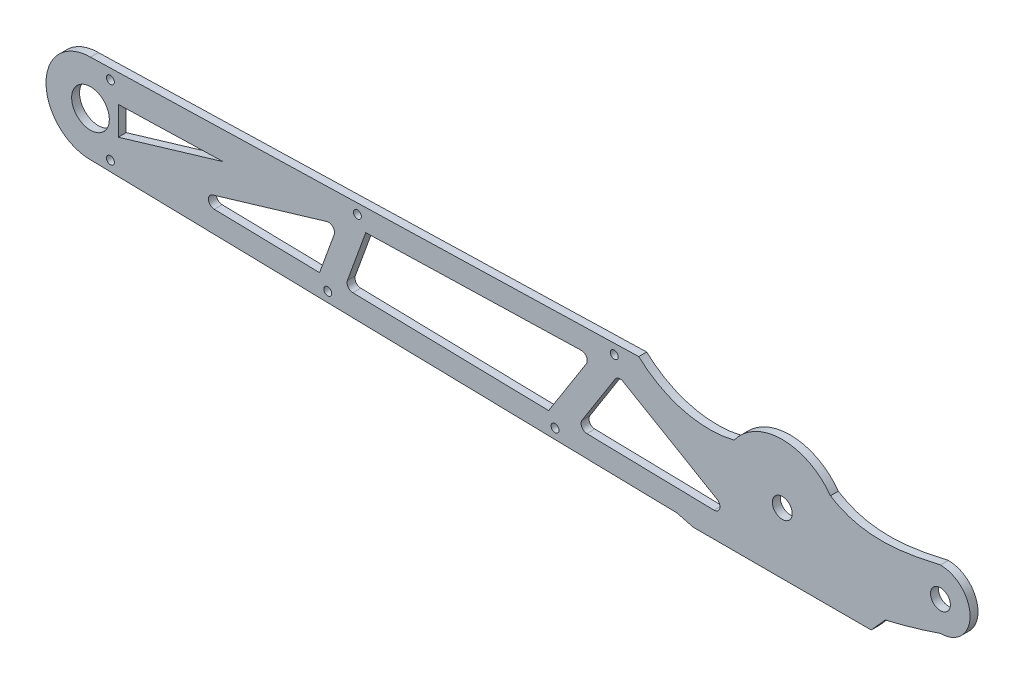
SolidWorks part; units mm, degrees
ref_plane "前视基准面" through (0, 0, 0) normal (0, 0, 1) x (1, 0, 0)
ref_plane "上视基准面" through (0, 0, 0) normal (0, 1, 0) x (1, 0, 0)
ref_plane "右视基准面" through (0, 0, 0) normal (1, 0, 0) x (0, 0, -1)
sketch "草图1" plane through (0, 0, 0) normal (0, 0, 1) x (1, 0, 0)
  line L1 (-1.4571, -0.1457) -> (348.5429, -0.1457) construction
  line L4 (348.5429, -0.1457) -> (428.5429, -0.1457) construction
  line L9 (-1.4571, -22.6457) -> (348.5429, -30.1457)
  line L10 (275.9324, 29.8543) -> (-1.4571, 22.3543)
  circle A0 centre (428.5429, -0.1457) radius 5.03
  circle A1 centre (-1.4571, -0.1457) radius 9.53
  circle A4 centre (-1.4571, -0.1457) radius 22.5 construction
  circle A11 centre (348.5429, -0.1457) radius 5.03
  circle A14 centre (348.5429, -0.1457) radius 30 construction
  circle A15 centre (428.5429, -0.1457) radius 15 construction
  arc A16 (428.5429, -15.1457) -> (428.5429, 14.8543) centre (428.5429, -0.1457) ccw
  arc A18 (372.8996, 17.3685) -> (324.1861, 17.3685) centre (348.5429, -0.1457) ccw
  arc A19 (428.5429, -15.1457) -> (348.5429, -30.1457) centre (338.2377, 245.6483) cw
  arc A20 (324.1861, 17.3685) -> (275.9324, 29.8543) centre (311.6087, 68.2465) cw
  arc A21 (-1.4571, -22.6457) -> (-1.4571, 22.3543) centre (-1.4571, -0.1457) cw
  spline S0 degree 3 poles (428.5429, 14.8543) (410.6193, 10.8049) (389.6426, 6.6246) (372.8996, 17.3685) knots 0 0 0 0 1 1 1 1
  dimension "D1" = 350
  dimension "D2" = 10.06
  dimension "D3" = 19.06
  dimension "D4" = 10.06
  dimension "D5" = 45
  dimension "D7" = 80
extrude "凸台-拉伸1" add sketch "草图1" along normal blind 4
sketch "草图2" plane through (0, 0, 4) normal (0, 0, 1) x (1, 0, 0)
  line L0 (348.5429, -30.1457) -> (348.5429, -25.1457)
  line L2 (-1.4571, -0.1457) -> (348.5429, -0.1457) construction
  circle A0 centre (348.5429, -25.1457) radius 2 construction
  circle A1 centre (233.5693, -22.682) radius 2
  circle A2 centre (118.5956, -20.2183) radius 2
  circle A3 centre (3.622, -17.7546) radius 2 construction
  circle A4 centre (3.622, 17.4631) radius 2 construction
  circle A5 centre (133.5745, 20.9768) radius 2
  circle A6 centre (263.5271, 24.4904) radius 2
  circle A7 centre (8.622, -17.7546) radius 2
  circle A8 centre (8.622, 17.4631) radius 2
  dimension "D1" = 4
  dimension "D3" = 5
  dimension "D2" = 3
extrude "切除-拉伸1" cut sketch "草图2" against normal blind 4 contours A3 | A4 | A1 | A0 | A6 | A7 | A8 | A5 | A2 region at (233.5693, -22.682, 4) region at (263.5271, 24.4904, 4) region at (8.622, -17.7546, 4) region at (8.622, 17.4631, 4)
sketch "草图3" plane through (0, 0, 4) normal (0, 0, 1) x (1, 0, 0)
  line L0 (348.5429, -25.1457) -> (233.5693, -22.682) construction
  line L1 (233.5693, -22.682) -> (263.5271, 24.4904) construction
  line L2 (263.5271, 24.4904) -> (348.5429, -25.1457) construction
  line L3 (267.9891, 14.9375) -> (315.5193, -12.8128)
  line L4 (313.9424, -18.4029) -> (249.6636, -17.0255)
  line L5 (247.1954, -12.4179) -> (263.944, 13.955)
  line L6 (233.5693, -22.682) -> (118.5956, -20.2183) construction
  line L7 (118.5956, -20.2183) -> (133.5745, 20.9768) construction
  line L8 (133.5745, 20.9768) -> (263.5271, 24.4904) construction
  line L9 (230.3171, -16.6109) -> (131.2818, -14.4887)
  line L10 (128.5266, -10.4643) -> (137.8181, 15.0893)
  line L11 (137.8181, 15.0893) -> (246.7805, 18.0354)
  line L12 (230.3171, -16.6109) -> (249.3941, 13.4282)
  line L13 (118.5956, -20.2183) -> (3.622, -17.7546) construction
  line L14 (3.622, -17.7546) -> (133.5745, 20.9768) construction
  line L15 (114.426, -14.1275) -> (61.1321, -12.9855)
  line L16 (60.3395, -7.1112) -> (118.1475, 10.118)
  line L17 (114.426, -14.1275) -> (121.8237, 6.2178)
  line L18 (133.5745, 20.9768) -> (3.622, 17.4631) construction
  line L19 (3.622, 17.4631) -> (3.622, -17.7546) construction
  line L20 (12.622, -5.6809) -> (65.6992, 10.1383)
  line L21 (65.6992, 10.1383) -> (12.622, 8.7032)
  line L22 (12.622, 8.7032) -> (12.622, -5.6809)
  line L23 (42.0049, -12.5757) -> (123.8611, 11.8209) construction
  line L24 (114.426, -14.1275) -> (42.0049, -12.5757) construction
  line L25 (114.426, -14.1275) -> (123.8611, 11.8209) construction
  line L26 (127.0959, -14.399) -> (137.8181, 15.0893) construction
  line L27 (230.3171, -16.6109) -> (127.0959, -14.399) construction
  line L28 (137.8181, 15.0893) -> (252.4168, 18.1878) construction
  line L29 (230.3171, -16.6109) -> (252.4168, 18.1878) construction
  line L30 (244.3416, -16.9115) -> (265.4934, 16.3946) construction
  line L31 (325.5187, -18.651) -> (244.3416, -16.9115) construction
  line L32 (265.4934, 16.3946) -> (325.5187, -18.651) construction
  arc A0 (60.3395, -7.1112) -> (61.1321, -12.9855) centre (61.1963, -9.9862) ccw
  arc A1 (118.1475, 10.118) -> (121.8237, 6.2178) centre (119.0043, 7.243) cw
  arc A2 (128.5266, -10.4643) -> (131.2818, -14.4887) centre (131.346, -11.4894) ccw
  arc A3 (246.7805, 18.0354) -> (249.3941, 13.4282) centre (246.8616, 15.0365) cw
  arc A4 (247.1954, -12.4179) -> (249.6636, -17.0255) centre (249.7278, -14.0262) ccw
  arc A5 (263.944, 13.955) -> (267.9891, 14.9375) centre (266.4765, 12.3467) cw
  arc A6 (313.9424, -18.4029) -> (315.5193, -12.8128) centre (314.0067, -15.4036) ccw
  dimension "D5" = 3
  dimension "D1" = 6
  dimension "D2" = 6
  dimension "D3" = 6
  dimension "D4" = 9
extrude "切除-拉伸2" cut sketch "草图3" against normal blind 10
sketch "草图5" plane through (0, 0, 4) normal (0, 0, 1) x (1, 0, 0)
  line L0 (348.5429, -0.1457) -> (348.5429, -31.1457) construction
  line L1 (348.5429, -31.1457) -> (303.5429, -31.1457)
  line L3 (348.5429, -31.1457) -> (393.5429, -31.1457)
  line L5 (393.5429, -31.1457) -> (400.6394, -23.191)
  line L6 (400.6394, -23.191) -> (348.5429, -15.6457)
  line L7 (303.5429, -31.1457) -> (295.2483, -29.0037)
  line L8 (-1.4571, -22.6457) -> (348.5429, -30.1457) construction
  line L9 (295.2483, -29.0037) -> (348.5429, -15.6457)
  arc A0 (348.5429, -30.1457) -> (428.5429, -15.1457) centre (338.2377, 245.6483) ccw construction
extrude "凸台-拉伸2" add sketch "草图5" against normal blind 4
